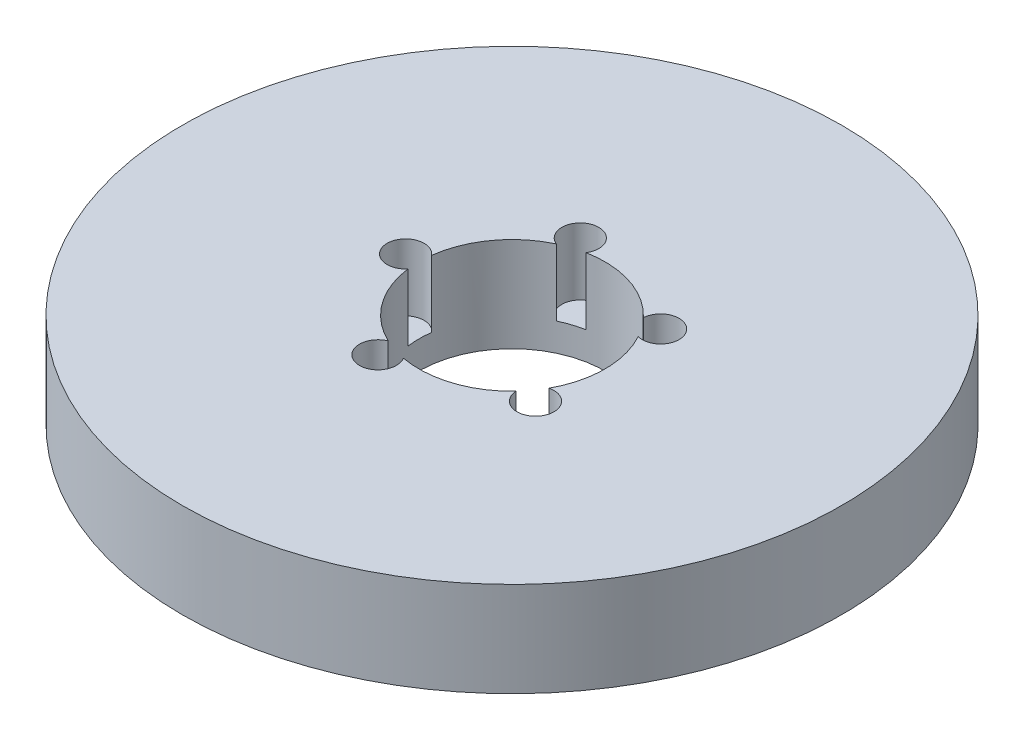
SolidWorks part; units mm, degrees
ref_plane "Front Plane" through (0, 0, 0) normal (0, 0, 1) x (1, 0, 0)
ref_plane "Top Plane" through (0, 0, 0) normal (0, 1, 0) x (1, 0, 0)
ref_plane "Right Plane" through (0, 0, 0) normal (1, 0, 0) x (0, 0, -1)
sketch "Sketch1" plane through (0, 0, 0) normal (0, 1, 0) x (1, 0, 0)
  circle A0 centre (0, 0) radius 97.5
  dimension "FLANGE_OD" = 195
extrude "Boss-Extrude1" add sketch "Sketch1" along normal blind 28
sketch "Sketch2" plane through (0, 0, 0) normal (0, 1, 0) x (1, 0, 0)
  circle A0 centre (0, 0) radius 27.5
  dimension "BORE_D" = 55
extrude "Cut-Extrude1" cut sketch "Sketch2" along normal through all
sketch "Sketch3" plane through (0, 28, 0) normal (0, 1, 0) x (1, 0, 0)
  circle A0 centre (0, 0) radius 31.4751 construction
  circle A1 centre (-31.4751, 0) radius 5.4645
  dimension "BOLT_D" = 10.929
  dimension "BOLT_PCD" = 62.9502
extrude "Cut-Extrude2" cut sketch "Sketch3" against normal blind 19.7501
pattern_circular "CirPattern1" count 5 over 360 about axis through (0, 0, 0) along (0, 1, 0) of "Cut-Extrude2"
